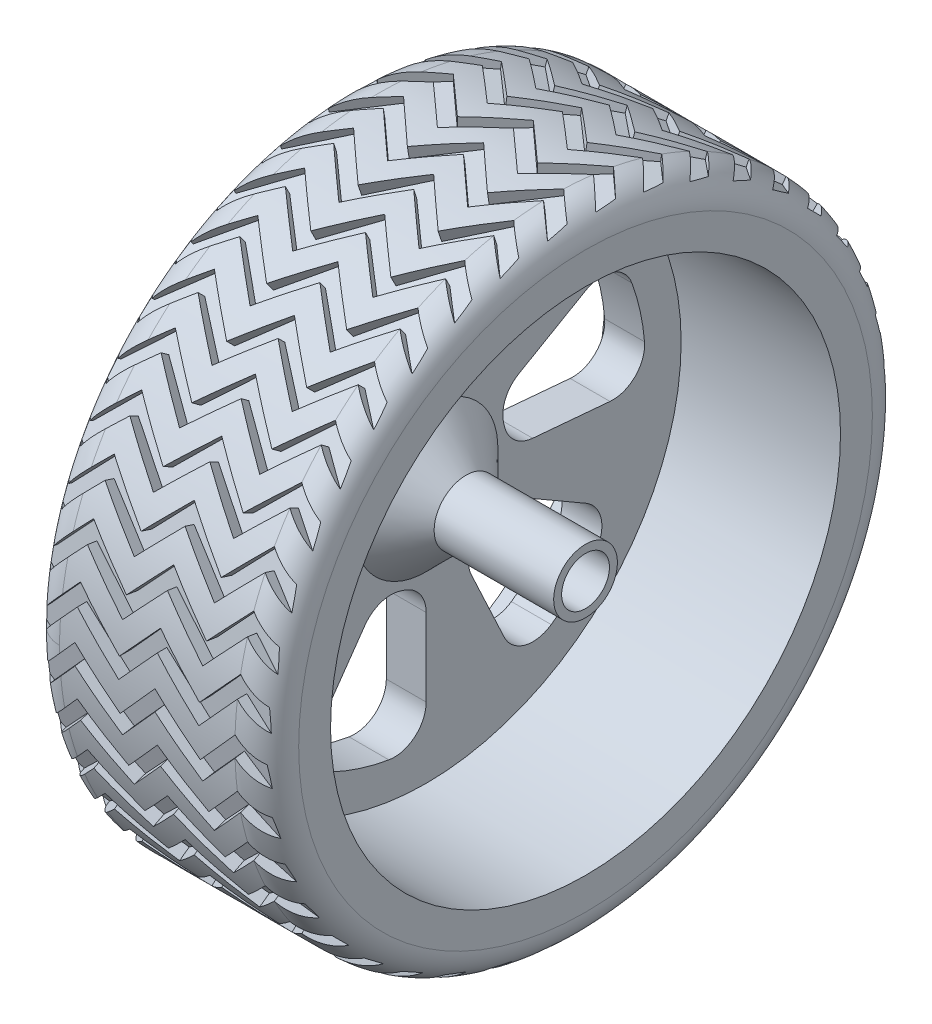
SolidWorks part; units mm, degrees
ref_plane "前视基准面" through (0, 0, 0) normal (0, 0, 1) x (1, 0, 0)
ref_plane "上视基准面" through (0, 0, 0) normal (0, 1, 0) x (1, 0, 0)
ref_plane "右视基准面" through (0, 0, 0) normal (1, 0, 0) x (0, 0, -1)
other "Configuration Table"
sketch "草图1" plane through (0, 0, 0) normal (0, 1, 0) x (1, 0, 0)
  line L0 (30, 32) -> (30, 36)
  line L1 (5, 0) -> (30, 0)
  line L2 (0, 32.4272) -> (0, 36)
  line L3 (4, 40) -> (26, 40)
  line L4 (30, 0) -> (30, 4)
  line L5 (30, 32) -> (10, 32)
  line L7 (30, 4) -> (10, 4)
  line L8 (10, 32) -> (10, 4)
  line L9 (0, 32.4272) -> (5, 32.4272)
  line L12 (5, 32.4272) -> (5, 0)
  arc A0 (0, 36) -> (4, 40) centre (4, 36) cw
  arc A1 (30, 36) -> (26, 40) centre (26, 36) ccw
  point P7 (0, 40)
  point P10 (30, 40)
  dimension "D5" = 4
  dimension "D6" = 4
  dimension "D1" = 40
  dimension "D2" = 30
  dimension "D3" = 0
  dimension "D4" = 0
  dimension "D7" = 32.4272
  dimension "D8" = 25
  dimension "D9" = 5
  dimension "D10" = 4
  dimension "D11" = 8
revolve "旋转1" add sketch "草图1" angle 360 about L1
chamfer "倒角1" distance 5 angle 45 1 edges at (10, 0, 4)
sketch "草图12" plane through (10, 0, 0) normal (1, 0, 0) x (0, 0, -1)
  line L0 (0, 13.4164) -> (0, 23.1571)
  line L1 (7.6953, 10.9901) -> (13.2824, 18.9692)
  arc A0 (3.1562, 9.4888) -> (2.8571, 9.5831) centre (0, 0) ccw
  arc A1 (11.7088, 24.8828) -> (4.6809, 27.0987) centre (0, 0) ccw
  arc A2 (13.2824, 18.9692) -> (11.7088, 24.8828) centre (10.0057, 21.2635) ccw
  arc A3 (7.6953, 10.9901) -> (3.1562, 9.4888) centre (4.4187, 13.2844) cw
  arc A4 (0, 23.1571) -> (4.6809, 27.0987) centre (4, 23.1571) cw
  arc A5 (0, 13.4164) -> (2.8571, 9.5831) centre (4, 13.4164) ccw
  point P12 (0, 27.5)
  point P15 (0, 10)
  dimension "D1" = 55
  dimension "D2" = 20
  dimension "D4" = 4
  dimension "D3" = 35
extrude "切除-拉伸2" cut sketch "草图12" against normal blind 10 contours L1 A1 L0 A0 region at (10, 18.8227, -5.9348)
pattern_circular "阵列(圆周)1" count 6 over 360 about axis through (30, 0, 0) along (1, 0, 0) of "切除-拉伸2"
sketch "草图13" plane through (30, 0, 0) normal (1, 0, 0) x (0, 0, -1)
  circle A0 centre (0, 0) radius 3
  dimension "D1" = 6
extrude "切除-拉伸3" cut sketch "草图13" against normal blind 10
ref_plane "基准面1" through (0, 0, 38.5) normal (0, 0, 1) x (1, 0, 0)
sketch "草图14" plane through (0, 0, 38.5) normal (0, 0, 1) x (1, 0, 0)
  line L0 (-1.5443, 0) -> (31.5168, 0) construction
  line L1 (31.5168, 0) -> (26, 5)
  line L2 (26, 40) -> (26, -40) construction
  line L3 (26, 5) -> (21.4684, 0)
  line L4 (21.4684, 0) -> (15.9474, 5.0038)
  line L5 (15.9474, 5.0038) -> (11.4123, 0)
  line L6 (11.4123, 0) -> (5.9173, 4.9802)
  line L7 (5.9173, 4.9802) -> (1.4037, 0)
  line L8 (1.4037, 0) -> (-1.3547, 2.5)
  line L9 (31.5168, 2.5) -> (26, 7.5)
  line L10 (31.5168, 2.5) -> (-1.3547, 2.5) construction
  line L11 (26, 7.5) -> (21.4684, 2.5)
  line L12 (26, 7.5) -> (-1.5448, 7.5) construction
  line L13 (-1.5448, 7.5) -> (31.3564, 7.5) construction
  line L14 (21.4684, 2.5) -> (15.9516, 7.5)
  line L15 (15.9516, 7.5) -> (11.42, 2.5)
  line L16 (11.42, 2.5) -> (5.9032, 7.5)
  line L17 (5.9032, 7.5) -> (1.3716, 2.5)
  line L18 (1.3716, 2.5) -> (-1.3868, 5)
  line L19 (26, 5) -> (31.5794, 5)
  line L20 (31.5794, 5) -> (-1.3868, 5) construction
  line L21 (-1.3868, 5) -> (-1.3547, 2.5)
  line L22 (31.5168, 2.5) -> (31.5168, 0)
  dimension "D1" = 2.5
  dimension "D2" = 2.5
  dimension "D3" = 2.5
extrude "切除-拉伸4" cut sketch "草图14" along normal blind 10 contours L1 L22 L9 L11 L14 L15 L16 L17 L18 L21 L8 L7 L6 L5 L4 L3
pattern_circular "阵列(圆周)2" count 40 over 360 about axis through (5, 0, 0) along (-1, 0, 0) of "切除-拉伸4"
